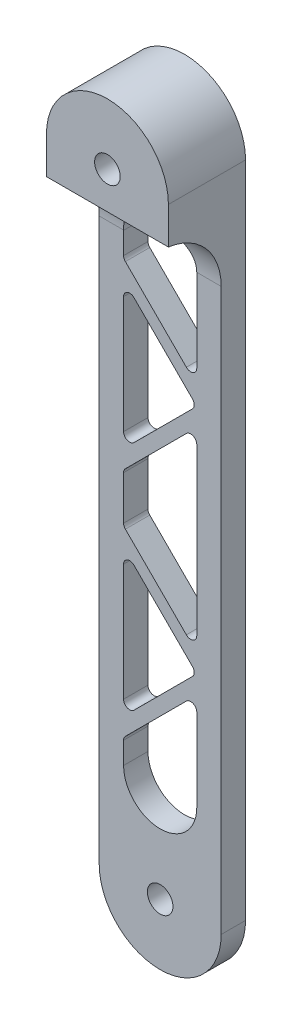
SolidWorks part; units mm, degrees
material "PLA"
ref_plane "Alzado" through (0, 0, 0) normal (0, 0, 1) x (1, 0, 0)
ref_plane "Planta" through (0, 0, 0) normal (0, 1, 0) x (1, 0, 0)
ref_plane "Vista lateral" through (0, 0, 0) normal (1, 0, 0) x (0, 0, -1)
sketch "Croquis1" plane through (0, 0, 0) normal (0, 0, 1) x (1, 0, 0)
  line L0 (0, 54) -> (0, -54) construction
  line L1 (10, 54) -> (10, -54)
  line L2 (-10, 54) -> (-10, -54)
  line L3 (0, 38) -> (0, -38) construction
  line L4 (6, 38) -> (6, -38)
  line L5 (-6, 38) -> (-6, -38)
  line L6 (-10, -47.95) -> (10, -47.95)
  line L7 (0, 51.9) -> (0, 44) construction
  line L8 (-10, 47.95) -> (10, 47.95)
  line L9 (0, -51.9) -> (0, -44) construction
  line L10 (-10, 0) -> (10, 0) construction
  line L11 (6, -19) -> (-6, -31)
  line L12 (-6, -34) -> (6, -22)
  line L13 (0, -38) -> (0, 0) construction
  line L14 (-6, -19) -> (6, -19) construction
  line L15 (-6, -4) -> (6, -16)
  line L16 (6, -19) -> (-6, -7)
  line L17 (-6, 4) -> (6, 16)
  line L18 (6, 19) -> (-6, 7)
  line L19 (6, 19) -> (-6, 31)
  line L20 (-6, 34) -> (6, 22)
  arc A0 (10, 54) -> (-10, 54) centre (0, 54) ccw
  arc A1 (-10, -54) -> (10, -54) centre (0, -54) ccw
  circle A2 centre (0, 54) radius 2.1
  circle A3 centre (0, -54) radius 2.1
  arc A4 (6, 38) -> (-6, 38) centre (0, 38) ccw
  arc A5 (-6, -38) -> (6, -38) centre (0, -38) ccw
  point P2 (0, 0)
  point P14 (0, 0)
  point P23 (0, 47.95)
  point P28 (0, -47.95)
  point P39 (0, -19)
  dimension "D1" = 4.2
  dimension "D2" = 20
  dimension "D3" = 108
  dimension "D4" = 4
  dimension "D5" = 16
  dimension "D6" = 135
  dimension "D7" = 3
extrude "Saliente-Extruir1" add sketch "Croquis1" along normal blind 4 contours L1 A0 L2 L8 A2 | L2 A1 L1 L8 A5 L5 A4 L4 A3 | L5 L12 L4 L11 | L16 L4 L15 L5 | L4 L18 L5 L17 | L20 L5 L19 L4 | L2 A1 L1 A0 | A3 | L5 A5 L4 A4 | A2 region at (9.7436, 50.975, 0) region at (9.0204, 0, 0) region at (0, 26.5, 0) region at (0, 11.5, 0) region at (0, -11.5, 0) region at (0, -26.5, 0)
extrude "Saliente-Extruir3" add sketch "Croquis1<6>" along normal up to surface (12.65 mm away) contours L1 A0 L2 L8 A2 region at (9.7436, 50.975, 0) up to face at (0, 34.5, 0)
sketch "Croquis1<6>" plane through (0, 0, 0) normal (0, 0, 1) x (1, 0, 0) same geometry as "Croquis1"
fillet "Redondeo1" radius 10 1 edges at (0, 47.95, 4)
fillet "Redondeo2" radius 1 14 edges at (-6, 34, 2) (6, 22, 2) (6, 19, 2) (-6, 31, 2) (-6, 7, 2) (6, 16, 2) (-6, -4, 2) (-6, 4, 2) (6, -16, 2) (6, -19, 2) (6, -22, 2) (-6, -31, 2) (-6, -7, 2) (-6, -34, 2)
